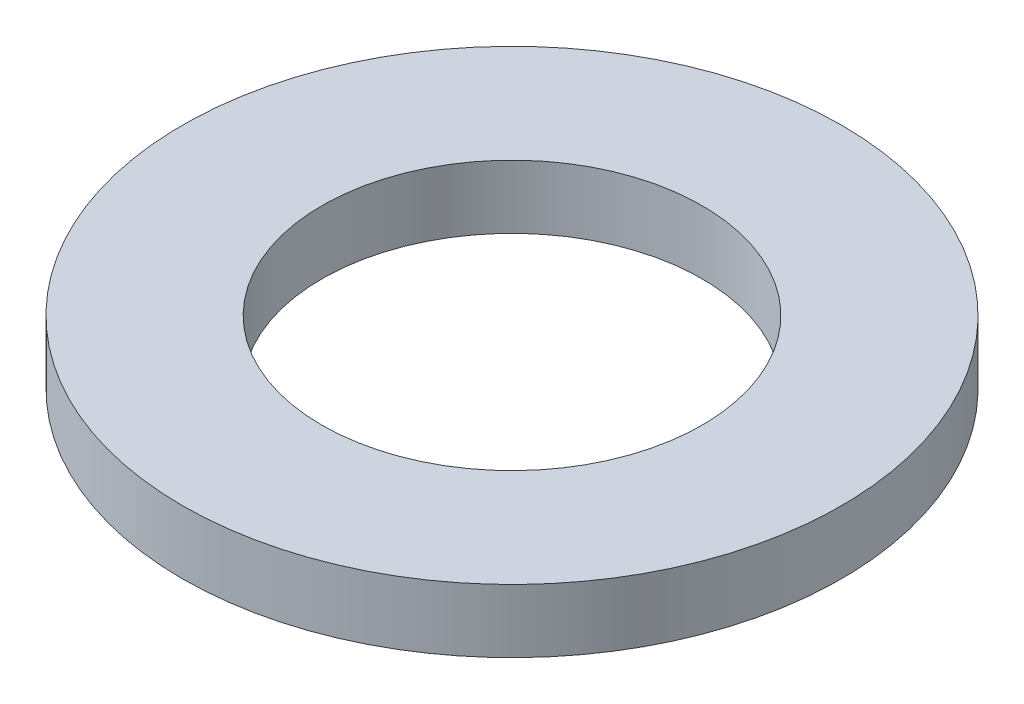
SolidWorks part; units mm, degrees
material "Balsa"
ref_plane "Front Plane" through (0, 0, 0) normal (0, 0, 1) x (1, 0, 0)
ref_plane "Top Plane" through (0, 0, 0) normal (0, 1, 0) x (1, 0, 0)
ref_plane "Right Plane" through (0, 0, 0) normal (1, 0, 0) x (0, 0, -1)
sketch "Sketch1" plane through (0, 0, 0) normal (0, 1, 0) x (1, 0, 0)
  circle A0 centre (0, 0) radius 66.04
  circle A1 centre (0, 0) radius 38.1
  dimension "D1" = 132.08
  dimension "D2" = 76.2
extrude "Boss-Extrude1" add sketch "Sketch1" along normal blind 12.7
